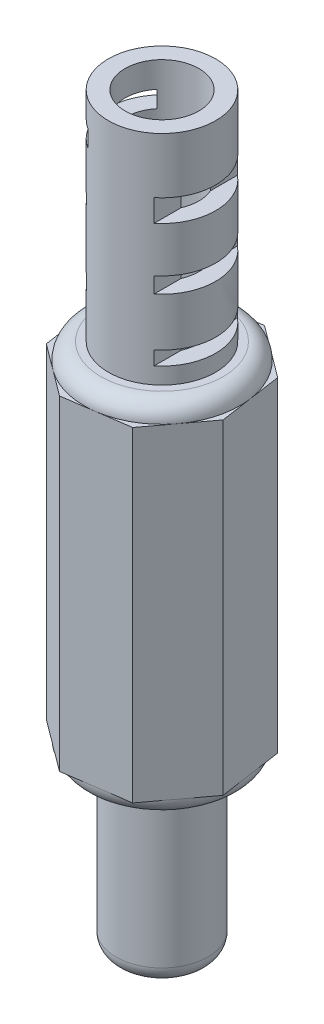
SolidWorks part; units mm, degrees
note: '?' marks a value the reader was unsure of.
material "PEI"
ref_plane "前视基准面" through (0, 0, 0) normal (0, 0, 1) x (1, 0, 0)
ref_plane "上视基准面" through (0, 0, 0) normal (0, 1, 0) x (1, 0, 0)
ref_plane "右视基准面" through (0, 0, 0) normal (1, 0, 0) x (0, 0, -1)
other "Configuration Table"
sketch "草图1" plane through (0, 0, 0) normal (0, 0, 1) x (1, 0, 0)
  line L0 (0, -4.6652) -> (0, 12.2768) construction
  line L1 (0, 0) -> (2.75, 0)
  line L2 (2.75, 0) -> (2.75, 10)
  line L3 (2.75, 10) -> (4.65, 10)
  line L4 (4.65, 10) -> (4.65, 31.4)
  line L5 (4.65, 31.4) -> (3.2, 31.4)
  line L6 (3.2, 31.4) -> (3.2, 44.4)
  line L7 (3.2, 44.4) -> (0, 44.4)
  line L8 (0, 44.4) -> (0, 0)
  line L9 (2, 0) -> (2, 15)
  line L10 (2, 15) -> (2.65, 15)
  line L11 (2.65, 15) -> (2.65, 26.4)
  line L12 (2.65, 26.4) -> (2.2, 26.4)
  line L13 (2.2, 26.4) -> (2.2, 44.4)
  dimension "D1" = 2.75
  dimension "D2" = 2
  dimension "D3" = 10
  dimension "D4" = 4.65
  dimension "D5" = 21.4
  dimension "D6" = 44.4
  dimension "D7" = 3.2
  dimension "D8" = 1
  dimension "D9" = 2
  dimension "D10" = 5
  dimension "D11" = 5
revolve "旋转1" add sketch "草图1" angle 360 about L0
fillet "圆角1" radius 1 3 edges at (0, 31.4, -4.65) (0, 10, -4.65) (0, 0, -2.75)
ref_plane "基准面1" through (0, 30.4, 0) normal (0, 1, 0) x (1, 0, 0)
sketch "草图2" plane through (0, 30.4, 0) normal (0, 1, 0) x (1, 0, 0)
  line L1 (1.235, 4.8793) -> (-2.5769, 4.3234)
  line L2 (-2.5769, 4.3234) -> (-4.8793, 1.235)
  line L3 (-4.8793, 1.235) -> (-4.3234, -2.5769)
  line L4 (-4.3234, -2.5769) -> (-1.235, -4.8793)
  line L5 (-1.235, -4.8793) -> (2.5769, -4.3234)
  line L6 (2.5769, -4.3234) -> (4.8793, -1.235)
  line L7 (4.8793, -1.235) -> (4.3234, 2.5769)
  line L8 (4.3234, 2.5769) -> (1.235, 4.8793)
  circle A0 centre (0, 0) radius 4.65 construction
  circle A1 centre (0, 0) radius 4.65 construction
  circle A2 centre (0, 0) radius 4.65
extrude "凸台-拉伸1" add sketch "草图2" against normal offset from surface (19.4 mm away) 1 contours L7 L8 L1 L2 L3 L4 L5 L6 | A2 L2 L3 | A2 L1 L2 | A2 L8 L1 | A2 L3 L4 | A2 L4 L5 | A2 L5 L6 | A2 L6 L7
sketch "草图3" plane through (0, 0, 0) normal (0, 0, 1) x (1, 0, 0)
  line L0 (3.65, 31.4) -> (-3.65, 31.4) construction
  line L1 (3.2, 44.4) -> (-3.2, 44.4) construction
  line L2 (3.2, 31.4) -> (3.2, 44.4) construction
  line L3 (-3.2, 44.4) -> (-3.2, 31.4) construction
  line L4 (3.65, 31.4) -> (-3.65, 31.4)
  line L5 (3.2, 44.4) -> (-3.2, 44.4)
  line L6 (3.2, 31.4) -> (3.2, 32.3843)
  line L7 (-3.2, 44.4) -> (-3.2, 42.8745)
  line L8 (3.2, 41.0771) -> (3.65, 41.0771)
  line L9 (-3.2, 42.8745) -> (-1.7, 42.8745)
  line L11 (-3.2, 41.8745) -> (-1.7, 41.8745)
  line L12 (-1.7, 42.8745) -> (-1.7, 41.8745)
  line L13 (-3.2, 39.1617) -> (-1.9602, 39.1617)
  line L15 (-3.2, 38.5134) -> (-1.9602, 38.5134)
  line L16 (-1.9602, 39.1617) -> (-1.9602, 38.5134)
  line L17 (-3.2, 35.0069) -> (-1.9602, 35.0069)
  line L19 (-3.2, 34.0639) -> (-1.9602, 34.0639)
  line L20 (-1.9602, 35.0069) -> (-1.9602, 34.0639)
  line L21 (3.2, 32.3843) -> (2.0178, 32.3843)
  line L23 (3.2, 33.2094) -> (2.0178, 33.2094)
  line L24 (2.0178, 32.3843) -> (2.0178, 33.2094)
  line L25 (3.2, 36.0972) -> (2.0178, 36.0972)
  line L27 (3.2, 37.0401) -> (2.0178, 37.0401)
  line L28 (2.0178, 36.0972) -> (2.0178, 37.0401)
  line L29 (3.2, 39.7511) -> (2.0178, 39.7511)
  line L31 (3.2, 41.0771) -> (2.0178, 41.0771)
  line L32 (2.0178, 39.7511) -> (2.0178, 41.0771)
  line L33 (-3.65, 31.4) -> (3.65, 31.4)
  line L34 (-3.65, 31.4) -> (-3.65, 44.4)
  line L35 (-3.65, 44.4) -> (3.65, 44.4)
  line L36 (3.65, 31.4) -> (3.65, 44.4)
  line L37 (3.65, 41.0771) -> (3.65, 39.7511)
  line L38 (3.65, 39.7511) -> (3.2, 39.7511)
  line L39 (3.2, 37.0401) -> (3.65, 37.0401)
  line L40 (3.65, 37.0401) -> (3.65, 36.0972)
  line L41 (3.65, 36.0972) -> (3.2, 36.0972)
  line L42 (3.2, 32.3843) -> (3.65, 32.3843)
  line L43 (3.65, 32.3843) -> (3.65, 33.2094)
  line L44 (3.65, 33.2094) -> (3.2777, 33.2094)
  line L45 (3.2777, 33.2094) -> (3.2, 33.2094)
  line L46 (-3.65, 34.0639) -> (-3.2, 34.0639)
  line L47 (-3.2, 35.0069) -> (-3.65, 35.0069)
  line L48 (-3.65, 35.0069) -> (-3.65, 38.5134)
  line L49 (-3.65, 38.5134) -> (-3.2, 38.5134)
  line L50 (-3.2, 39.1617) -> (-3.65, 39.1617)
  line L51 (-3.65, 39.1617) -> (-3.65, 41.8745)
  line L52 (-3.65, 41.8745) -> (-3.2, 41.8745)
  line L53 (-3.2638, 42.8745) -> (-3.65, 42.8745)
  line L54 (-3.65, 42.8745) -> (-3.2, 42.8745)
  line L55 (-3.2, 41.8745) -> (-3.2, 39.1617)
  line L56 (-3.2, 38.5134) -> (-3.2, 35.0069)
  line L57 (3.2, 41.0771) -> (3.2, 44.4)
  line L58 (3.2, 37.0401) -> (3.2, 39.7511)
  line L59 (-3.2, 34.0639) -> (-3.2, 31.4)
  line L60 (3.2, 33.2094) -> (3.2, 36.0972)
  dimension "D1" = 1.5
  dimension "D2" = 1
extrude "切除-拉伸8" cut sketch "草图3" against normal through all both and the other way through all contours L54 L53 L34 L52 L11 L12 L9 | L13 L50 L34 L49 L15 L16 | L17 L47 L34 L46 L19 L20 | L41 L36 L39 L27 L28 L25 | L38 L36 L8 L31 L32 L29 | L44 L45 L23 L24 L21 L42 L36
other "连接点1" parameters "直径"=4, "端头长度"=5
ref_axis "基准轴1" through (0, 49.1617, 0) along (0, -1, 0)?
